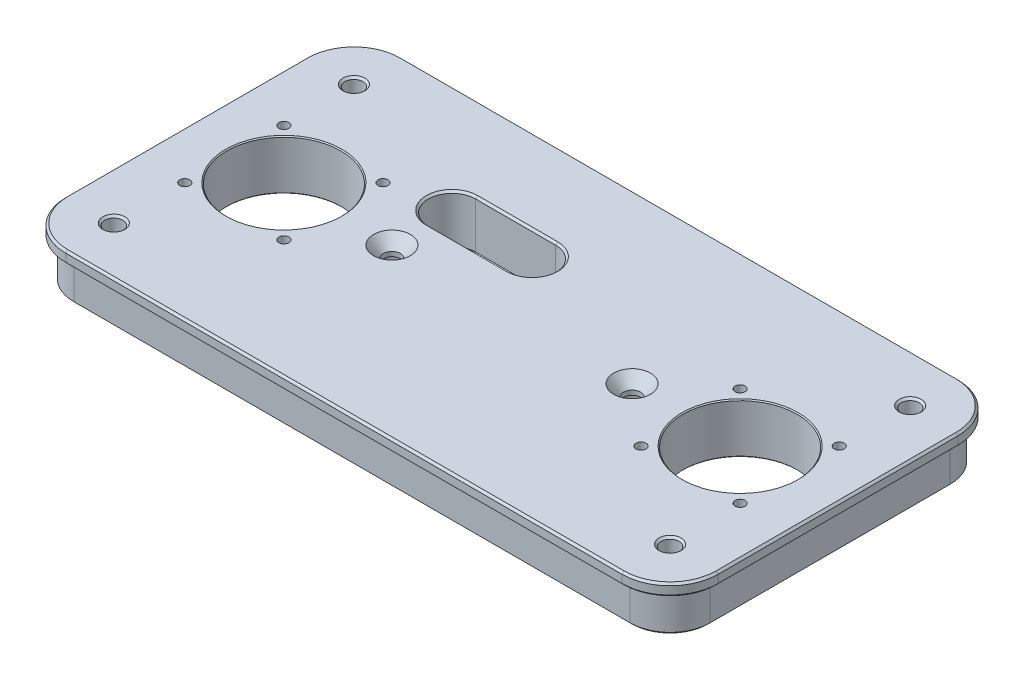
SolidWorks part; units mm, degrees
material "6061-T6 Aluminum"
ref_plane "Front Plane" through (0, 0, 0) normal (0, 0, 1) x (1, 0, 0)
ref_plane "Top Plane" through (0, 0, 0) normal (0, 1, 0) x (1, 0, 0)
ref_plane "Right Plane" through (0, 0, 0) normal (1, 0, 0) x (0, 0, -1)
sketch "Sketch1" plane through (0, 0, 0) normal (0, 1, 0) x (1, 0, 0)
  line L1 (-159, -80) -> (159, -80)
  line L2 (-159, -80) -> (-159, 80)
  line L3 (-159, 80) -> (159, 80)
  line L4 (159, -80) -> (159, 80)
  line L5 (-159, -80) -> (159, 80) construction
  line L6 (-159, 80) -> (159, -80) construction
  point P0 (0, 0)
  dimension "D1" = 160
  dimension "D2" = 318
extrude "Boss-Extrude1" add sketch "Sketch1" along normal blind 25
sketch "Sketch2" plane through (0, 25, 0) normal (0, 1, 0) x (1, 0, 0)
  line L0 (-114, 0) -> (0, 0) construction
  line L1 (0, 0) -> (114, 0) construction
  circle A0 centre (-114, 0) radius 28.5
  circle A1 centre (114, 0) radius 28.5
  dimension "D1" = 228
  dimension "D2" = 57
extrude "Cut-Extrude1" cut sketch "Sketch2" against normal through all
sketch "Sketch4" plane through (0, 25, 0) normal (0, 1, 0) x (1, 0, 0)
  line L0 (60, 0) -> (0, 0) construction
  line L1 (0, 0) -> (-60, 0) construction
  circle A0 centre (-60, 0) radius 9.55
  circle A1 centre (60, 0) radius 9.55
  dimension "D1" = 19.1
  dimension "D2" = 120
extrude "Cut-Extrude2" cut sketch "Sketch4" against normal through all both and the other way through all
chamfer "Chamfer1" distance 0.5 angle 45 8 edges at (114, 25, 28.5) (114, 0, 28.5) (60, 25, -9.55) (60, 0, 9.55) (-60, 25, -9.55) (-60, 0, 9.55) (-114, 25, 28.5) (-114, 0, 28.5)
fillet "Fillet1" radius 20 4 edges at (159, 12.5, 80) (159, 12.5, -80) (-159, 12.5, -80) (-159, 12.5, 80)
hole_wizard "M8 Clearance Hole1" positions "Sketch5" profile "Sketch6" hole size "M8" standard "ANSI Metric" end condition through all
sketch "Sketch5" plane through (0, 0, 0) normal (0, 1, 0) x (1, 0, 0)
  point P0 (-139, 60)
  point P3 (-139, -60)
  point P6 (139, 60)
  point P9 (139, -60)
sketch "Sketch6" plane through (-139, 0, -60) normal (1, 0, 0) x (0, 0, -1)
  line L0 (0, 0) -> (0, 25)
  line L1 (0, 25) -> (4.5, 25)
  line L2 (4.5, 25) -> (4.5, 0)
  line L5 (4.5, 0) -> (0, 0)
  line L11 (0, -6.35) -> (0, 107.95) construction
  dimension "Thru Hole Dia." = 9
  dimension "Thru Hole Depth" = 25
sketch "Sketch7" plane through (0, 0, 0) normal (0, -1, 0) x (1, 0, 0)
  line L1 (89.235, 24.765) -> (138.765, 24.765) construction
  line L2 (89.235, 24.765) -> (89.235, -24.765) construction
  line L3 (89.235, -24.765) -> (138.765, -24.765) construction
  line L4 (138.765, 24.765) -> (138.765, -24.765) construction
  line L5 (89.235, 24.765) -> (138.765, -24.765) construction
  line L6 (89.235, -24.765) -> (138.765, 24.765) construction
  line L7 (-138.765, 24.765) -> (-89.235, 24.765) construction
  line L8 (-138.765, 24.765) -> (-138.765, -24.765) construction
  line L9 (-138.765, -24.765) -> (-89.235, -24.765) construction
  line L10 (-89.235, 24.765) -> (-89.235, -24.765) construction
  line L11 (-138.765, 24.765) -> (-89.235, -24.765) construction
  line L12 (-138.765, -24.765) -> (-89.235, 24.765) construction
  circle A0 centre (89.235, 24.765) radius 3.302 construction
  circle A1 centre (138.765, -24.765) radius 3.302 construction
  circle A2 centre (138.765, 24.765) radius 3.302 construction
  circle A3 centre (89.235, -24.765) radius 3.302 construction
  circle A4 centre (89.235, 24.765) radius 3.302
  circle A5 centre (138.765, -24.765) radius 3.302
  circle A6 centre (138.765, 24.765) radius 3.302
  circle A7 centre (89.235, -24.765) radius 3.302
  circle A12 centre (-138.765, -24.765) radius 3.302
  circle A13 centre (-89.235, -24.765) radius 3.302
  circle A14 centre (-89.235, 24.765) radius 3.302
  circle A15 centre (-138.765, 24.765) radius 3.302
  point P13 (114, 0)
  point P15 (-114, 0)
hole_wizard "M6x1.0 Tapped Hole1" positions "Sketch8" profile "Sketch9" tap size "M6x1.0" standard "ANSI Metric" end condition through all
sketch "Sketch8" plane through (0, 0, 0) normal (0, -1, 0) x (-1, 0, 0)
  point P0 (138.765, -24.765)
  point P3 (89.235, -24.765)
  point P6 (89.235, 24.765)
  point P9 (138.765, 24.765)
  point P12 (-89.235, -24.765)
  point P15 (-138.765, -24.765)
  point P18 (-89.235, 24.765)
  point P21 (-138.765, 24.765)
cosmetic thread "Hole Thread11" parameters "D2"=6
cosmetic thread "Hole Thread12" parameters "D2"=6
cosmetic thread "Hole Thread13" parameters "D2"=6
cosmetic thread "Hole Thread14" parameters "D2"=6
cosmetic thread "Hole Thread16" parameters "D2"=6
sketch "Sketch9" plane through (-138.765, 0, 24.765) normal (1, 0, 0) x (0, 0, -1)
  line L0 (0, 0) -> (0, 25)
  line L1 (0, 25) -> (2.5, 25)
  line L2 (2.5, 25) -> (2.5, 0)
  line L5 (2.5, 0) -> (0, 0)
  line L11 (0, -6.35) -> (0, 107.95) construction
  dimension "Thru Tap Drill Dia." = 5
  dimension "Thru Tap Drill Depth" = 25
cosmetic thread "Hole Thread17" parameters "D2"=6
cosmetic thread "Hole Thread18" parameters "D2"=6
cosmetic thread "Hole Thread19" parameters "D2"=6
sketch "Sketch13" plane through (0, 25, 0) normal (0, 1, 0) x (1, 0, 0)
  circle A0 centre (60, 0) radius 13.411
  circle A1 centre (-60, 0) radius 14.7245
extrude "Boss-Extrude3" add sketch "Sketch13" against normal blind 8
hole_wizard "CSK for 5/16 Flat Head Socket Cap Screw1" positions "Sketch14" profile "Sketch15" countersink size "5/16" standard "ANSI Inch" end condition through all
sketch "Sketch14" plane through (0, 25, 0) normal (0, 1, 0) x (1, 0, 0)
  point P0 (60, 0)
  point P3 (-60, 0)
sketch "Sketch15" plane through (60, 25, 0) normal (1, 0, 0) x (0, 0, 1)
  line L0 (0, 0) -> (0, 25)
  line L1 (0, 25) -> (4.2164, 25)
  line L2 (4.2164, 25) -> (4.2164, 5.7335)
  line L3 (4.2164, 5.7335) -> (9.2005, 0)
  line L5 (9.2005, 0) -> (0, 0)
  line L6 (-4.2164, 5.7335) -> (-9.2005, 0) construction
  line L11 (0, -6.35) -> (0, 107.95) construction
  dimension "Thru Hole Dia." = 8.4328
  dimension "Thru Hole Depth" = 25
  dimension "Near C'Sink Dia." = 18.401
  dimension "Near C'Sink Angle" = 82
sketch "Sketch16" plane through (0, 25, 0) normal (0, -1, 0) x (1, 0, 0)
  line L4 (159, 60) -> (159, -60) construction
  line L5 (139, -80) -> (-139, -80) construction
  line L6 (-159, -60) -> (-159, 60) construction
  line L7 (-139, 80) -> (139, 80) construction
  line L8 (163, -60) -> (163, 60)
  line L9 (139, 84) -> (-139, 84)
  line L10 (-163, 60) -> (-163, -60)
  line L11 (-139, -84) -> (139, -84)
  line L12 (163, -60) -> (163, 60)
  line L13 (139, 84) -> (-139, 84)
  line L14 (-163, 60) -> (-163, -60)
  line L15 (-139, -84) -> (139, -84)
  line L16 (159, 60) -> (159, -60)
  line L17 (139, -80) -> (-139, -80)
  line L18 (-159, -60) -> (-159, 60)
  line L19 (-139, 80) -> (139, 80)
  arc A4 (159, 60) -> (139, 80) centre (139, 60) ccw construction
  arc A5 (139, -80) -> (159, -60) centre (139, -60) ccw construction
  arc A6 (-159, -60) -> (-139, -80) centre (-139, -60) ccw construction
  arc A7 (-139, 80) -> (-159, 60) centre (-139, 60) ccw construction
  arc A8 (163, 60) -> (139, 84) centre (139, 60) ccw
  arc A9 (-139, 84) -> (-163, 60) centre (-139, 60) ccw
  arc A10 (-163, -60) -> (-139, -84) centre (-139, -60) ccw
  arc A11 (139, -84) -> (163, -60) centre (139, -60) ccw
  arc A12 (163, 60) -> (139, 84) centre (139, 60) ccw
  arc A13 (-139, 84) -> (-163, 60) centre (-139, 60) ccw
  arc A14 (-163, -60) -> (-139, -84) centre (-139, -60) ccw
  arc A15 (139, -84) -> (163, -60) centre (139, -60) ccw
  arc A16 (159, 60) -> (139, 80) centre (139, 60) ccw
  arc A17 (139, -80) -> (159, -60) centre (139, -60) ccw
  arc A18 (-159, -60) -> (-139, -80) centre (-139, -60) ccw
  arc A19 (-139, 80) -> (-159, 60) centre (-139, 60) ccw
  dimension "D1" = 4
extrude "Boss-Extrude4" add sketch "Sketch16" along normal blind 6
sketch "Sketch17" plane through (0, 0, 0) normal (0, -1, 0) x (1, 0, 0)
  line L0 (-60, -30.0192) -> (-20, -30.0192) construction
  line L1 (-60, -18.1841) -> (-20, -18.1841)
  line L2 (-60, -41.8544) -> (-20, -41.8544)
  circle A0 centre (-60, -30.0192) radius 9.2363 construction
  arc A1 (-69.9426, -35.7596) -> (-50.0574, -35.7596) centre (-60, -30.0192) ccw construction
  arc A2 (-60, -18.1841) -> (-60, -41.8544) centre (-60, -30.0192) ccw
  arc A3 (-20, -41.8544) -> (-20, -18.1841) centre (-20, -30.0192) ccw
  point P2 (-40, -30.0192)
  dimension "D1" = 40
extrude "Cut-Extrude3" cut sketch "Sketch17" against normal through all
chamfer "Chamfer4" distance 1 angle 45 40 edges at (139, 0, -64.5) (139, 25, -64.5) (-139, 0, -64.5) (-139, 25, -64.5) (139, 0, 55.5) (139, 25, 55.5) (-139, 0, 55.5) (-139, 25, 55.5) (0, 19, -84) (155.9706, 19, -76.9706) (-155.9706, 19, -76.9706) (163, 19, 0) (-163, 19, 0) (155.9706, 19, 76.9706) (-155.9706, 19, 76.9706) (0, 19, 84) (0, 25, -84) (155.9706, 25, -76.9706) (-155.9706, 25, -76.9706) (163, 25, 0) (-163, 25, 0) (155.9706, 25, 76.9706) (-155.9706, 25, 76.9706) (0, 25, 84) (-40, 25, -18.1841) (-71.8351, 25, -30.0192) (-8.1649, 25, -30.0192) (-40, 25, -41.8544) (-40, 0, -18.1841) (-71.8351, 0, -30.0192) (-8.1649, 0, -30.0192) (-40, 0, -41.8544) (0, 0, -80) (-153.1421, 0, -74.1421) (153.1421, 0, -74.1421) (-159, 0, 0) (159, 0, 0) (-153.1421, 0, 74.1421) (153.1421, 0, 74.1421) (0, 0, 80)
sketch "Sketch18" plane through (0, 0, 0) normal (0, -1, 0) x (1, 0, 0)
  circle A0 centre (-105, -70) radius 3.25 construction
  circle A1 centre (-75, -70) radius 3.25 construction
  circle A2 centre (-45, -70) radius 3.25 construction
  circle A3 centre (-15, -70) radius 3.25 construction
  circle A4 centre (15, -70) radius 3.25 construction
  circle A5 centre (45, -70) radius 3.25 construction
  circle A6 centre (75, -70) radius 3.25 construction
  circle A7 centre (105, -70) radius 3.25 construction
  circle A8 centre (-105, -70) radius 3.25
  circle A9 centre (-75, -70) radius 3.25
  circle A10 centre (-45, -70) radius 3.25
  circle A11 centre (-15, -70) radius 3.25
  circle A12 centre (15, -70) radius 3.25
  circle A13 centre (45, -70) radius 3.25
  circle A14 centre (75, -70) radius 3.25
  circle A15 centre (105, -70) radius 3.25
  circle A16 centre (-105, 70) radius 3.25 construction
  circle A17 centre (-75, 70) radius 3.25 construction
  circle A18 centre (-45, 70) radius 3.25 construction
  circle A19 centre (-15, 70) radius 3.25 construction
  circle A20 centre (15, 70) radius 3.25 construction
  circle A21 centre (45, 70) radius 3.25 construction
  circle A22 centre (75, 70) radius 3.25 construction
  circle A23 centre (105, 70) radius 3.25 construction
  circle A24 centre (-105, 70) radius 3.25
  circle A25 centre (-75, 70) radius 3.25
  circle A26 centre (-45, 70) radius 3.25
  circle A27 centre (-15, 70) radius 3.25
  circle A28 centre (15, 70) radius 3.25
  circle A29 centre (45, 70) radius 3.25
  circle A30 centre (75, 70) radius 3.25
  circle A31 centre (105, 70) radius 3.25
hole_wizard "M6x1.0 Tapped Hole2" positions "Sketch19" profile "Sketch20" tap size "M6x1.0" standard "ANSI Metric"
sketch "Sketch19" plane through (0, 0, 0) normal (0, -1, 0) x (-1, 0, 0)
  point P1 (-75, 70)
  point P4 (-45, 70)
  point P7 (-105, 70)
  point P10 (-15, 70)
  point P13 (15, 70)
  point P16 (45, 70)
  point P19 (75, 70)
  point P22 (105, 70)
  point P25 (-105, -70)
  point P28 (-75, -70)
  point P31 (-45, -70)
  point P34 (-15, -70)
  point P37 (15, -70)
  point P40 (45, -70)
  point P43 (75, -70)
  point P46 (105, -70)
sketch "Sketch20" plane through (75, 0, -70) normal (1, 0, 0) x (0, 0, -1)
  line L0 (0, 0) -> (0, 16.5022)
  line L1 (0, 16.5022) -> (2.5, 15)
  line L2 (2.5, 15) -> (2.5, 0)
  line L5 (2.5, 0) -> (0, 0)
  line L10 (0, 16.5022) -> (-2.5, 15) construction
  line L11 (0, -6.35) -> (0, 107.95) construction
  dimension "Tap Drill Dia." = 5
  dimension "Tap Drill Depth" = 15
  dimension "Drill Angle" = 118
cosmetic thread "Hole Thread20" parameters "D1"=12, "D2"=6
cosmetic thread "Hole Thread21" parameters "D1"=12, "D2"=6
cosmetic thread "Hole Thread22" parameters "D1"=12, "D2"=6
cosmetic thread "Hole Thread23" parameters "D1"=12, "D2"=6
cosmetic thread "Hole Thread24" parameters "D1"=12, "D2"=6
cosmetic thread "Hole Thread25" parameters "D1"=12, "D2"=6
cosmetic thread "Hole Thread26" parameters "D1"=12, "D2"=6
cosmetic thread "Hole Thread27" parameters "D1"=12, "D2"=6
cosmetic thread "Hole Thread28" parameters "D1"=12, "D2"=6
cosmetic thread "Hole Thread29" parameters "D1"=12, "D2"=6
cosmetic thread "Hole Thread30" parameters "D1"=12, "D2"=6
cosmetic thread "Hole Thread31" parameters "D1"=12, "D2"=6
cosmetic thread "Hole Thread32" parameters "D1"=12, "D2"=6
cosmetic thread "Hole Thread33" parameters "D1"=12, "D2"=6
cosmetic thread "Hole Thread34" parameters "D1"=12, "D2"=6
cosmetic thread "Hole Thread35" parameters "D1"=12, "D2"=6
